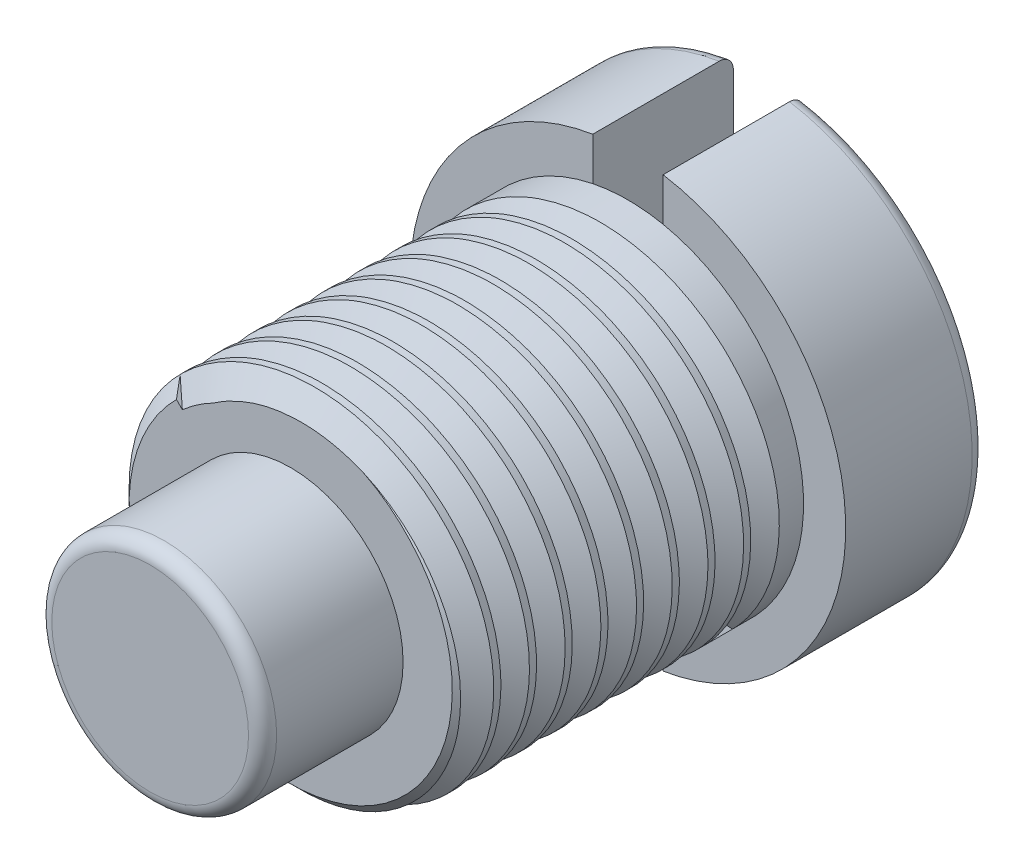
SolidWorks part; units mm, degrees
ref_plane "Front" through (0, 0, 0) normal (0, 0, 1) x (1, 0, 0)
ref_plane "Top" through (0, 0, 0) normal (0, 1, 0) x (1, 0, 0)
ref_plane "Right" through (0, 0, 0) normal (1, 0, 0) x (0, 0, -1)
sketch "Sketch1" plane through (0, 0, 0) normal (0, 0, 1) x (1, 0, 0)
  circle A0 centre (0, 0) radius 6.25
  dimension "D1" = 12.5
extrude "Boss-Extrude1" add sketch "Sketch1" along normal blind 12
sketch "Sketch2" plane through (0, 0, 0) normal (0, 0, -1) x (-1, 0, 0)
  circle A0 centre (0, 0) radius 7.75
  dimension "D1" = 15.5
extrude "Boss-Extrude2" add sketch "Sketch2" along normal blind 5
fillet "Fillet1" radius 0.5 1 edges at (-7.75, 0, -5)
sketch "Sketch3" plane through (0, 0, -5) normal (0, 0, -1) x (-1, 0, 0)
  line L0 (0, 9.1017) -> (0, -9.2927) construction
  line L1 (-1.25, 9.1017) -> (1.25, 9.1017)
  line L2 (-1.25, 9.1017) -> (-1.25, -9.2927)
  line L3 (-1.25, -9.2927) -> (1.25, -9.2927)
  line L4 (1.25, 9.1017) -> (1.25, -9.2927)
  circle A0 centre (0, 0) radius 7.25 construction
  circle A1 centre (0, 0) radius 7.25
  circle M7 centre (0, 0) radius 7.25
  dimension "D1" = 2.5
extrude "Cut-Extrude1" cut sketch "Sketch3" against normal blind 5 contours L0 A1 L2 M7 | L0 A1 L4 M7 | A1 L0 L3 L4 | L0 L2 L3 M7 | L1 L0 L4 M7 | L0 L1 L2 A1
chamfer "Chamfer1" distance 0.5 angle 45 1 edges at (6.25, 0, 12)
sketch "Sketch5" plane through (0, 0, 12) normal (0, 0, 1) x (1, 0, 0)
  circle A0 centre (0, 0) radius 6.25 construction
  circle A1 centre (0, 0) radius 6.25
curve "Helix/Spiral1" pitch 1.27 height 10.795 turns 8.5
ref_plane "Plane1" through (-4.4194, 4.4194, 12) normal (0.7067, 0.7067, -0.0323) x (0.7075, -0.706, 0.0323)
sketch "Sketch6" plane through (-4.4194, 4.4194, 12) normal (0.7067, 0.7067, -0.0323) x (0.7075, -0.706, 0.0323)
  line L1 (-0.2105, -0.6516) -> (0.8807, -0.0216)
  line L2 (0.8807, -0.0216) -> (-0.2105, 0.6084)
  line L3 (-0.2105, 0.6084) -> (-0.2105, -0.6516)
  circle A0 centre (0.1532, -0.0216) radius 0.3637 construction
  point P1 (0.1532, -0.0216)
  dimension "D1" = 1.26
sweep "Cut-Sweep1" cut profiles "Sketch6" path "Helix/Spiral1"
sketch "Sketch7" plane through (0, 0, 12) normal (0, 0, 1) x (1, 0, 0)
  circle A0 centre (0, 0) radius 4
  dimension "D1" = 8
extrude "Cut-Extrude2" cut sketch "Sketch7" against normal blind 10
sketch "Sketch8" plane through (0, 0, 2) normal (0, 0, 1) x (1, 0, 0)
  circle A1 centre (0, 0) radius 4
  circle A2 centre (0, 0) radius 4
  dimension "D1" = 0
extrude "Boss-Extrude3" add sketch "Sketch8" along normal blind 15 separate body
fillet "Fillet2" radius 0.5 1 edges at (4, 0, 17)
